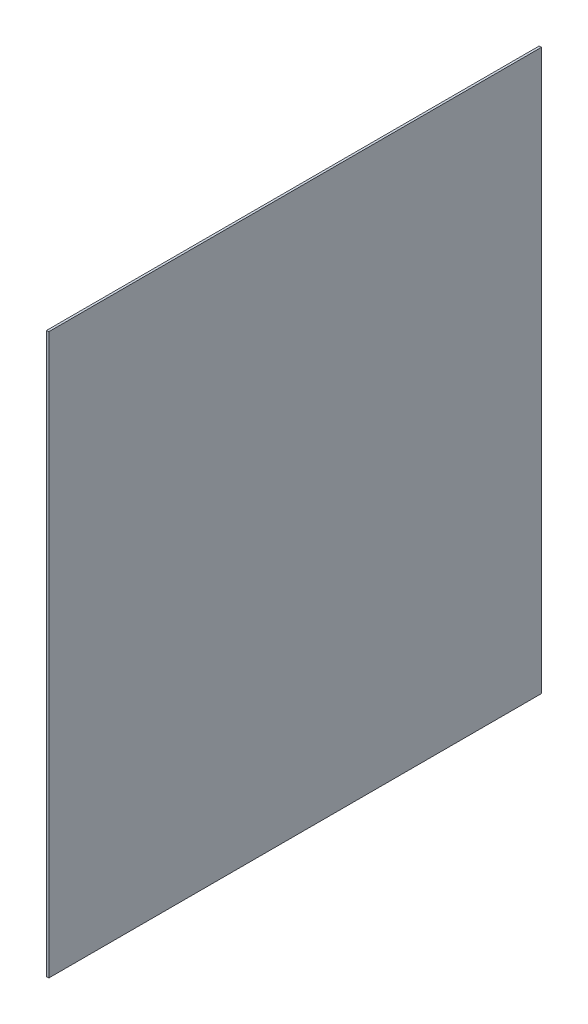
SolidWorks part; units mm, degrees
ref_plane "Спереди" through (0, 0, 0) normal (0, 0, 1) x (1, 0, 0)
ref_plane "Сверху" through (0, 0, 0) normal (0, 1, 0) x (1, 0, 0)
ref_plane "Справа" through (0, 0, 0) normal (1, 0, 0) x (0, 0, -1)
sketch "Эскиз1" plane through (0, 0, 0) normal (0, 0, 1) x (1, 0, 0)
  line L0 (0, 0) -> (0, 500)
  dimension "D1" = 500
sheet metal parameters "Листовой металл1" thickness 2 parameters "D1"=1.8, "Толщина"=2
base flange "Базовая кромка1" sketch "Эскиз1" end condition blind depth 440 reverse direction no thickness 2 reverse thickness direction no bend radius 1.8
flat pattern "Развертка1" [suppressed]
sketch "Сгиб-Линии1" plane through (0, 0, 0) normal (0, 1, 0) x (-1, 0, 0)
sketch3d "Граничная рамка1" [suppressed]
  line L0 (0, 500, 0) -> (0, 0, 0) construction
  line L1 (-440, 500, 0) -> (-440, 0, 0) construction
  line L2 (0, 500, 0) -> (-440, 500, 0) construction
  line L3 (0, 0, 0) -> (-440, 0, 0) construction
